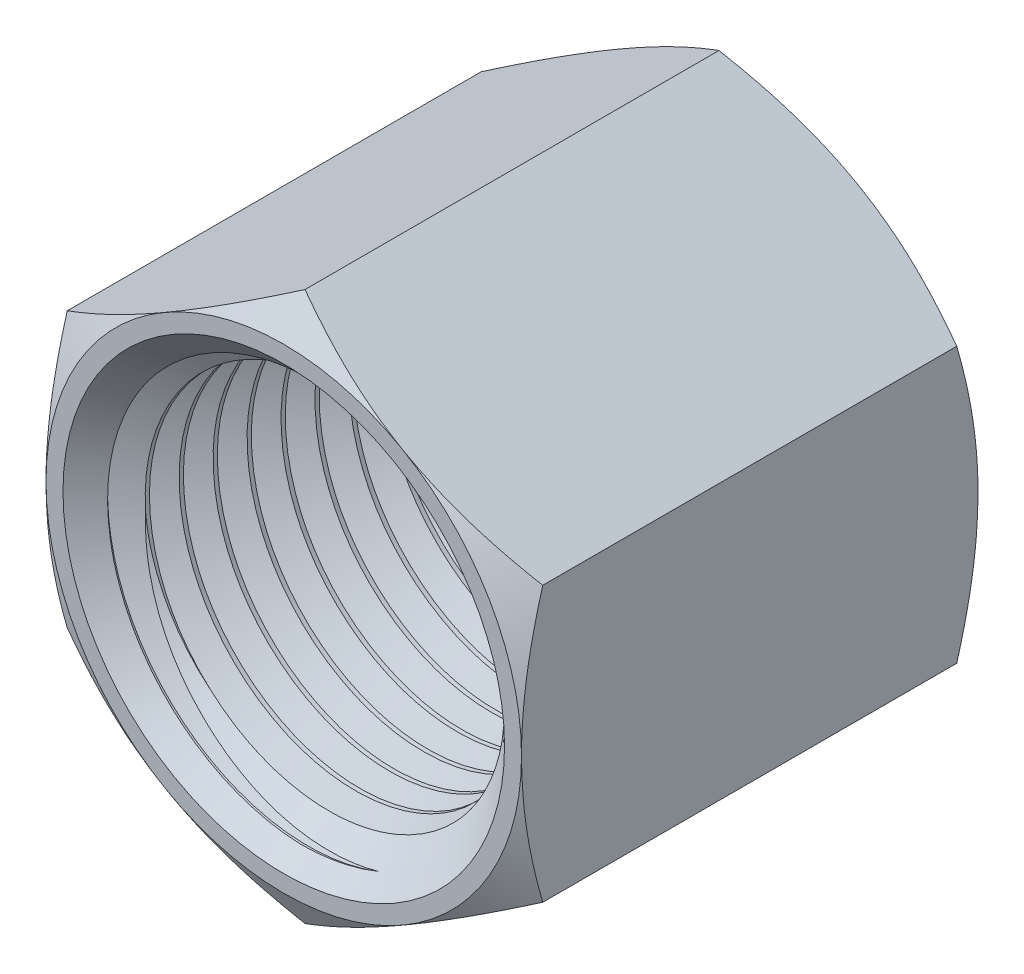
SolidWorks part; units mm, degrees
ref_plane "Front Plane" through (0, 0, 0) normal (0, 0, 1) x (1, 0, 0)
ref_plane "Top Plane" through (0, 0, 0) normal (0, 1, 0) x (1, 0, 0)
ref_plane "Right Plane" through (0, 0, 0) normal (1, 0, 0) x (0, 0, -1)
sketch "Sketch1" plane through (0, 0, 0) normal (1, 0, 0) x (0, 0, -1)
  line L0 (-10.668, 0) -> (10.668, 0) construction
  line L1 (-10.668, 9.525) -> (-10.668, -9.525) construction
  line L2 (0, -11.1125) -> (0, 11.1125) construction
  line L3 (10.668, 7.239) -> (10.668, -7.239) construction
  line L4 (-10.668, 9.525) -> (-12.2555, 9.525) construction
  line L5 (-10.668, 11.1125) -> (10.668, 11.1125) construction
  line L6 (0, 9.525) -> (2.667, 9.525) construction
  line L7 (2.667, 9.525) -> (5.334, 9.525) construction
  line L8 (5.334, 9.525) -> (8.001, 9.525) construction
  line L9 (8.001, 9.525) -> (10.668, 9.525) construction
  line L10 (-10.668, 9.525) -> (0, 9.525) construction
  line L11 (2.667, 9.525) -> (8.001, 7.239) construction
  line L12 (8.001, 7.239) -> (10.668, 7.239) construction
  line L13 (-10.668, -9.525) -> (0, -9.525) construction
  line L14 (0, -9.525) -> (2.667, -9.525) construction
  line L15 (2.667, -9.525) -> (8.001, -7.239) construction
  line L16 (8.001, -7.239) -> (10.668, -7.239) construction
  point P2 (0, 0)
  point P6 (-10.668, 0)
  point P9 (0, 0)
  point P12 (10.668, 0)
  point P15 (0, 11.1125)
  point P17 (10.668, -7.239)
  dimension "Tube" = 14.478
  dimension "Thread" = 19.05
  dimension "Hex" = 22.225
  dimension "Length" = 21.336
  dimension "Pitch" = 1.5875
sketch "Sketch1A" plane through (0, 0, 0) normal (0, 0, 1) x (1, 0, 0)
  line L0 (-7.239, 0) -> (7.239, 0) construction
  line L1 (0, 12.8316) -> (-11.1125, 6.4158) construction
  line L2 (-11.1125, 6.4158) -> (-11.1125, -6.4158) construction
  line L3 (-11.1125, -6.4158) -> (0, -12.8316) construction
  line L4 (0, -12.8316) -> (11.1125, -6.4158) construction
  line L5 (11.1125, -6.4158) -> (11.1125, 6.4158) construction
  line L6 (11.1125, 6.4158) -> (0, 12.8316) construction
  line L7 (0, 7.239) -> (0, -7.239) construction
  line L8 (0, -11.1125) -> (0, 11.1125) construction
  circle A0 centre (0, 0) radius 11.1125 construction
  point P1 (0, 0)
  point P15 (0, -9.525)
ref_plane "Plane1" through (0, 0, 10.668) normal (0, 0, 1) x (1, 0, 0)
sketch "Sketch2" plane through (0, 0, 0) normal (0, 0, 1) x (1, 0, 0)
  line L0 (0, 7.239) -> (0, -7.239) construction
  line L1 (0, 12.8316) -> (-11.1125, 6.4158)
  line L2 (-11.1125, 6.4158) -> (-11.1125, -6.4158)
  line L3 (-11.1125, -6.4158) -> (0, -12.8316)
  line L4 (0, -12.8316) -> (11.1125, -6.4158)
  line L5 (11.1125, -6.4158) -> (11.1125, 6.4158)
  line L6 (11.1125, 6.4158) -> (0, 12.8316)
  circle A0 centre (0, 0) radius 11.1125 construction
  circle A1 centre (0, 0) radius 7.239
extrude "Boss-Extrude1" add sketch "Sketch2" along normal up to vertex (10.668 mm away) and the other way up to vertex (10.668 mm away) up to point (0, 0, 10.668) other way up to point (0, 0, -10.668)
sketch "Sketch3" plane through (0, 0, 0) normal (1, 0, 0) x (0, 0, -1)
  line L0 (-10.668, 9.525) -> (0, 9.525) construction
  line L1 (0, -11.1125) -> (0, 11.1125) construction
  line L2 (0, 9.525) -> (2.667, 9.525) construction
  line L3 (2.667, 9.525) -> (5.334, 9.525) construction
  line L4 (5.334, 9.525) -> (8.001, 9.525) construction
  line L5 (8.001, 9.525) -> (10.668, 9.525) construction
  line L6 (10.668, 6.4158) -> (10.668, 12.8316) construction
  line L7 (-10.668, 9.525) -> (2.667, 9.525)
  line L8 (2.667, 9.525) -> (8.001, 7.239)
  line L9 (8.001, 7.239) -> (10.668, 7.239)
  line L10 (-10.668, 9.525) -> (-10.668, 0)
  line L11 (-10.668, 0) -> (10.668, 0)
  line L12 (10.668, 0) -> (10.668, 7.239)
revolve "Cut-Revolve1" cut sketch "Sketch3" angle 360 about L11
sketch "Sketch4" plane through (0, 0, 10.668) normal (0, 0, 1) x (1, 0, 0)
  circle A0 centre (0, 0) radius 11.1125
extrude "Cut-Extrude1" cut sketch "Sketch4" against normal blind 2.54 draft 60 flip side to cut
mirror "Mirror1" about plane through (0, 0, 0) normal (0, 0, 1) of "Cut-Extrude1"
sketch "Sketch5" plane through (0, 0, 10.668) normal (0, 0, 1) x (1, 0, 0)
  circle A0 centre (0, 0) radius 9.525
curve "Helix/Spiral1" pitch 1.5875 height 16.002 turns 10.08
sketch "Sketch6" plane through (0, 0, 0) normal (1, 0, 0) x (0, 0, -1)
  line L0 (-12.2059, 9.6109) -> (-10.6184, 9.6109) construction
  line L1 (-10.6184, 9.6109) -> (-11.4121, 8.2361) construction
  line L2 (-11.4121, 8.2361) -> (-12.2059, 9.6109) construction
  line L3 (-11.4121, 8.2361) -> (-11.4121, 8.408) construction
  line L4 (-11.4121, 8.408) -> (-11.4121, 9.4391) construction
  line L5 (-11.4121, 9.4391) -> (-11.4121, 9.6109) construction
  line L6 (-11.5114, 8.408) -> (-11.3129, 8.408) construction
  line L7 (-10.668, 9.525) -> (-11.3129, 8.408)
  line L8 (-10.7176, 9.4391) -> (-12.1067, 9.4391) construction
  line L9 (-11.3129, 8.408) -> (-11.5114, 8.408)
  line L10 (-10.668, 9.525) -> (-12.1563, 9.525) construction
  line L11 (-11.5114, 8.408) -> (-12.1563, 9.525)
  line L12 (-12.1563, 9.525) -> (-10.668, 9.525)
  point P12 (-11.4121, 8.408)
  point P14 (-11.4121, 9.4391)
  point P15 (-11.4121, 9.525)
  point P16 (-11.4121, 9.525)
  dimension "D1" = 1.5875
  dimension "D2" = 0.1984
sweep "Sweep1" add profiles "Sketch6" path "Helix/Spiral1"
sketch "Sketch7" plane through (0, 0, 10.668) normal (0, 0, 1) x (1, 0, 0)
  circle A0 centre (0, 0) radius 10.3187
  dimension "D1" = 20.6375
extrude "Cut-Extrude2" cut sketch "Sketch7" against normal blind 2.54 draft 45 and the other way through all
equation "\"D3@Helix/Spiral1\"=\"Length@Sketch1\"*.75"
equation "\"D4@Helix/Spiral1\"=\"Pitch@Sketch1\""
equation "\"D1@Sketch6\"=\"Pitch@Sketch1\""
equation "\"D2@Sketch6\"=\"D1@Sketch6\"/8"
equation "\"D1@Sketch7\"=\"Thread@Sketch1\"+\"Pitch@Sketch1\""
